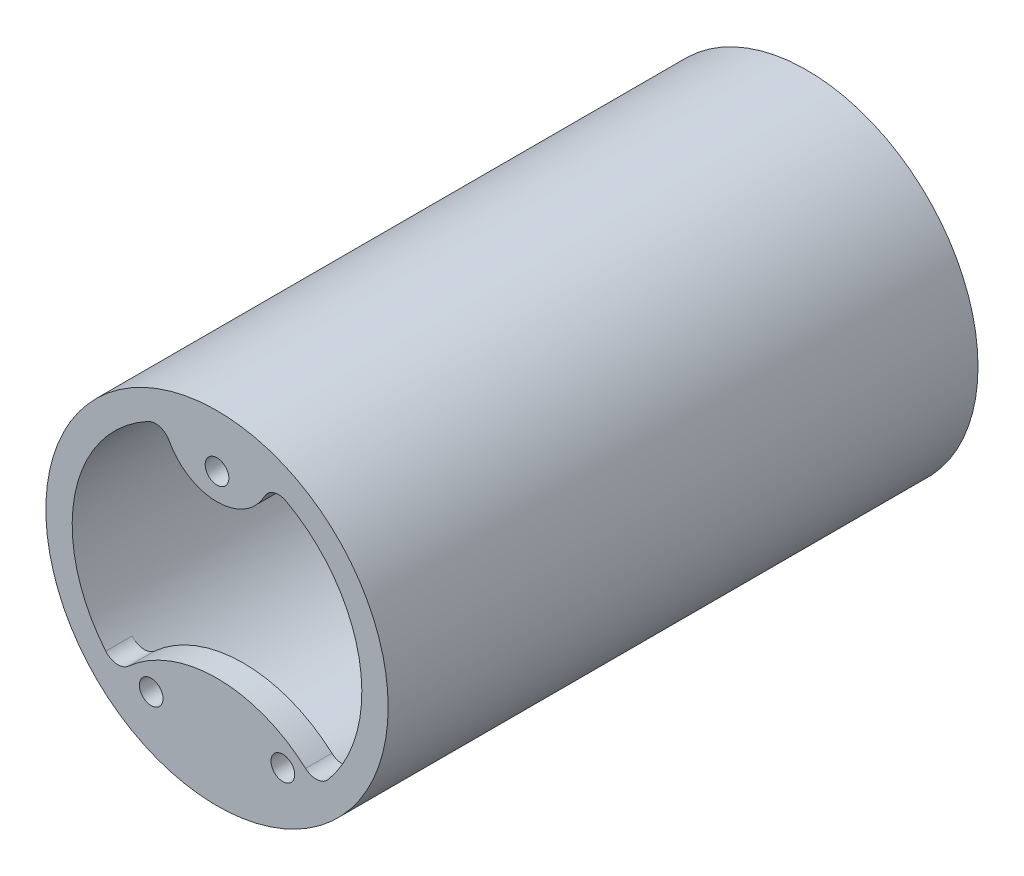
SolidWorks part; units mm, degrees
ref_plane "Alzado" through (0, 0, 0) normal (0, 0, 1) x (1, 0, 0)
ref_plane "Planta" through (0, 0, 0) normal (0, 1, 0) x (1, 0, 0)
ref_plane "Vista lateral" through (0, 0, 0) normal (1, 0, 0) x (0, 0, -1)
sketch "Croquis1" plane through (0, 0, 0) normal (0, 0, 1) x (1, 0, 0)
  circle A0 centre (0, 0) radius 32.5
  circle A1 centre (0, 0) radius 27.5
  dimension "D1" = 65
  dimension "D2" = 5
extrude "Boss-Extrude1" add sketch "Croquis1" along normal blind 112
sketch "Sketch1" plane through (0, 0, 0) normal (0, 0, -1) x (-1, 0, 0)
  line L0 (0, 0) -> (11.3818, 0) construction
  circle A0 centre (-30, 0) radius 1.5
  circle A1 centre (0, 30) radius 1.5
  circle A2 centre (30, 0) radius 1.5
  circle A3 centre (0, -30) radius 1.5
  circle A7 centre (0, 0) radius 30 construction
  circle A8 centre (0, 0) radius 27.5 construction
  point P17 (0, 0)
  dimension "D1" = 2.5
  dimension "D2" = 3
  dimension "D3" = 0
  dimension "D4" = 4
extrude "Cut-Extrude1" cut sketch "Sketch1" against normal blind 5
sketch "Sketch4" plane through (0, 0, 112) normal (0, 0, 1) x (1, 0, 0)
  arc A0 (-10, 25.6174) -> (10, 25.6174) centre (0, 27.7183) ccw
  circle A1 centre (0, 0) radius 27.5 construction
  circle A2 centre (0, 0) radius 27.5 construction
  arc A3 (-10, 25.6174) -> (10, 25.6174) centre (0, 0) cw
  circle A4 centre (0, 0) radius 27.5 construction
  arc A5 (-18.8746, -20) -> (18.8746, -20) centre (0, -36.7059) cw
  arc A6 (-18.8746, -20) -> (18.8746, -20) centre (0, 0) ccw
  point P1 (0, 17.5)
  point P9 (0, 27.5)
  point P11 (0, -27.5)
  point P14 (0, -11.5)
  dimension "D1" = 10
  dimension "D3" = 16
  dimension "D2" = 10
  dimension "D5" = 20
extrude "Boss-Extrude4" add sketch "Sketch4" against normal blind 5
sketch "Sketch2" plane through (0, 0, 112) normal (0, 0, 1) x (1, 0, 0)
  circle A0 centre (-12.5, -20) radius 2.25
  circle A1 centre (12.5, -20) radius 2.25
  circle A2 centre (0, 22.5) radius 2.25
  dimension "D5" = 4.5
  dimension "D6" = 4.5
  dimension "D7" = 4.5
  dimension "D1" = 25
  dimension "D2" = 22.5
  dimension "D3" = 20
  dimension "D4" = 12.5
extrude "Cut-Extrude2" cut sketch "Sketch2" against normal blind 5
fillet "Fillet1" radius 3 4 edges at (18.8746, -20, 109.5) (-18.8746, -20, 109.5) (10, 25.6174, 109.5) (-10, 25.6174, 109.5)
equation "\"D6@Sketch2\"=\"D5@Sketch2\""
equation "\"D7@Sketch2\"=\"D5@Sketch2\""
equation "\"D4@Sketch2\"=\"D1@Sketch2\"/2"
